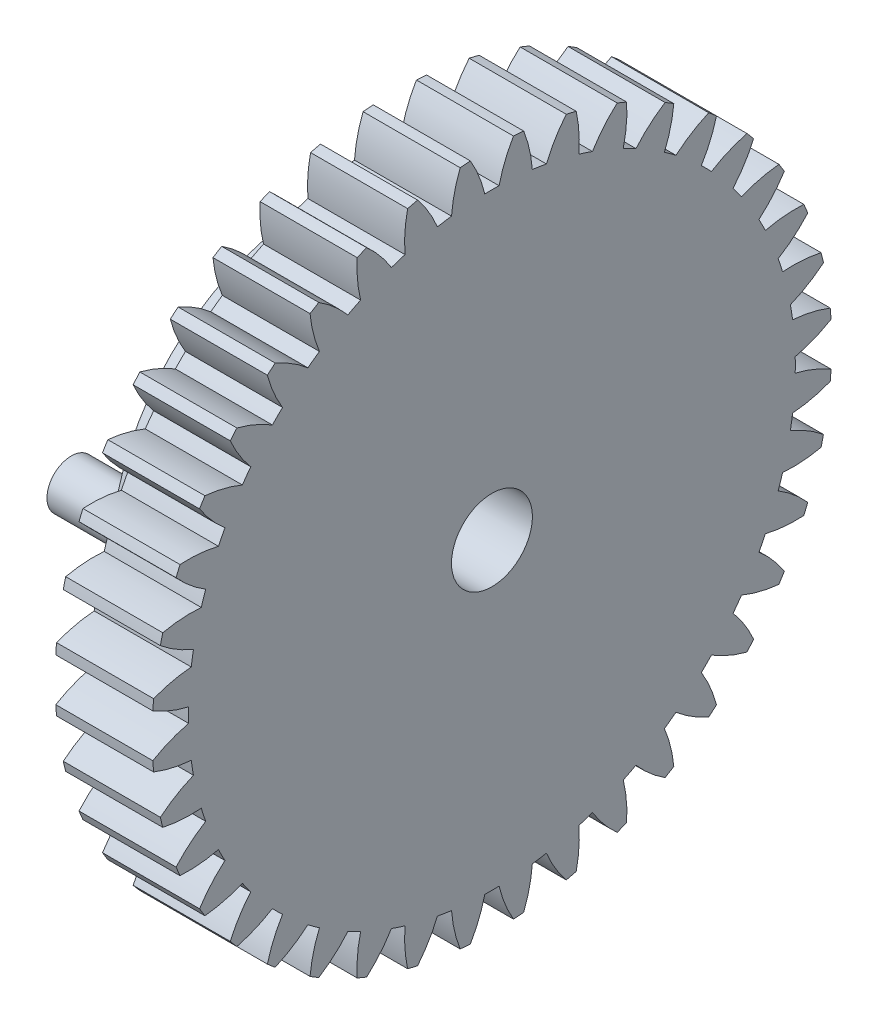
SolidWorks part; units mm, degrees
ref_plane "Plane1" through (0, 0, 0) normal (0, 0, 1) x (1, 0, 0)
ref_plane "Plane2" through (0, 0, 0) normal (0, 1, 0) x (1, 0, 0)
ref_plane "Plane3" through (0, 0, 0) normal (1, 0, 0) x (0, 0, -1)
sketch "HoldingSke" plane through (0, 0, 0) normal (0, 1, 0) x (1, 0, 0)
  line L0 (0, 0) -> (0.383, -0.3214)
  line L1 (-15, 0) -> (100, 0) construction
  line L2 (0, 0) -> (-2.1039, 2.3779)
  line L3 (0, 0) -> (-11.863, 4.5341)
  line L4 (0, 0) -> (6.6156, 5.5511)
  line L5 (0, 0) -> (-46.8476, -17.4728)
  line L6 (0, 0) -> (-9.9476, -6.7116)
  line L7 (-2.1039, 2.3779) -> (8.6586, 51.2059)
  line L8 (-76.2, 54.61) -> (-74.4, 54.61)
  line L9 (-71.009, 38.7566) -> (-53.1078, 45.2721)
  line L10 (-76.2, 71.12) -> (104.1128, 71.12)
  line L11 (0, 0) -> (-12, 0)
  line L12 (-76.2, 101.6) -> (-76.133, 101.6)
  line L13 (24.9733, 27.94) -> (52.9518, 28.4284)
  line L14 (24.9733, 27.94) -> (24.9743, 27.94)
  line L15 (24.9733, 27.94) -> (100.4006, 29.5858)
  line L16 (-63.627, -2) -> (-12.827, -2)
  circle A0 centre (0, 0) radius 5
  circle A1 centre (0, 0) radius 37.499
  circle A2 centre (0, 0) radius 37.5
  circle A3 centre (0, 0) radius 5
  dimension "Num_teeth" = 40
  dimension "Pitch_radius" = 180.3128
  dimension "Width" = 12
  dimension "Thickness" = 12
sketch "BasProSke" plane through (0, 0, 0) normal (0, 1, 0) x (1, 0, 0)
  line L0 (-10, 0) -> (60, 0) construction
  line L1 (0, 0) -> (0, 42)
  line L2 (0, 0) -> (12, 0)
  line L3 (12, 0) -> (12, 42)
  line L4 (12, 42) -> (0, 42)
  dimension "Thickness" = 12
  dimension "Diameter" = 84
revolve "Base-Revolve" add sketch "BasProSke" angle 360 about L0
sketch "TooCutSke" plane through (0, 0, 0) normal (1, 0, 0) x (0, 0, -1)
  line L1 (0, 0) -> (0, 107) construction
  line L2 (0, 0) -> (-1.6876, 39.9644) construction
  line L3 (0, 0) -> (-6.2726, 79.7007) construction
  line L4 (-1.6876, 39.9644) -> (-3.1363, 39.8504) construction
  arc A0 (0.8828, 37.4886) -> (-0.8828, 37.4886) centre (0, 0) ccw
  arc A1 (2.6784, 41.94) -> (-2.6784, 41.94) centre (0, 0) ccw
  circle A2 centre (0, 0) radius 40 construction
  circle A3 centre (0, 0) radius 37.5877 construction
  arc A4 (-0.8828, 37.4886) -> (-2.6784, 41.94) centre (-16.451, 33.7965) ccw
  arc A5 (2.6784, 41.94) -> (0.8828, 37.4886) centre (16.451, 33.7965) ccw
extrude "ToothCut" cut sketch "TooCutSke" along normal through all
fillet "Breaks" [suppressed] radius 0.04 tangent propagation no
fillet "RootFillets" [suppressed] radius 0.501
pattern_circular "TeethCuts" count 40 every 9 about axis through (-10, 0, 0) along (1, 0, 0) of "ToothCut", "RootFillets", "Breaks"
sketch "HubNeaOneSke" plane through (0, 0, 0) normal (-1, 0, 0) x (0, 0, 1)
  circle A0 centre (0, 0) radius 37.499
  dimension "Diameter" = 74.998
extrude "HubNearOne" [suppressed] add sketch "HubNeaOneSke" along normal blind 38.0001
sketch "HubNeaBotSke" plane through (0, 0, 0) normal (-1, 0, 0) x (0, 0, 1)
  circle A0 centre (0, 0) radius 37.499
  dimension "Diameter" = 74.998
extrude "HubNearBoth" [suppressed] add sketch "HubNeaBotSke" along normal blind 19
ref_plane "FarPln" through (12, 0, 0) normal (1, 0, 0) x (0, 0, -1)
sketch "HubFarSke" plane through (12, 0, 0) normal (1, 0, 0) x (0, 0, -1)
  circle A0 centre (0, 0) radius 37.499
  dimension "Diameter" = 74.998
extrude "HubFar" [suppressed] add sketch "HubFarSke" along normal blind 19
sketch "BorSke" plane through (0, 0, 0) normal (1, 0, 0) x (0, 0, -1)
  circle A0 centre (0, 0) radius 5
  dimension "Diameter" = 10
extrude "Bore" cut sketch "BorSke" along normal mid plane 100.0001
sketch "KeySke" plane through (0, 0, 0) normal (1, 0, 0) x (0, 0, -1)
  line L0 (-1.5, 0) -> (-1.5, 6.8)
  line L1 (-1.5, 6.8) -> (1.5, 6.8)
  line L2 (1.5, 6.8) -> (1.5, 0)
  line L3 (0, 0) -> (0, 34) construction
  line L4 (-1.5, 0) -> (1.5, 0)
  dimension "Width" = 3
extrude "Keyway" [suppressed] cut sketch "KeySke" along normal mid plane 100.0001
pattern_circular "Keyway2" [suppressed] count 2 every 90 about axis through (-10, 0, 0) along (1, 0, 0)
sketch "Sketch1" plane through (0, 0, 0) normal (-1, 0, 0) x (0, 0, 1)
  circle A0 centre (0, 0) radius 25
  circle A2 centre (0, 0) radius 5
  circle A3 centre (20, 0) radius 3
  circle A4 centre (-20, 0) radius 3
  point P16 (0, 0)
  dimension "D1" = 2
extrude "Boss-Extrude1" add sketch "Sketch1" along normal blind 10
extrude "Boss-Extrude2" add sketch "Sketch1<2>" along normal blind 20 separate body contours A4
sketch "Sketch1<2>" plane through (0, 0, 0) normal (-1, 0, 0) x (0, 0, 1) same geometry as "Sketch1"
extrude "Boss-Extrude3" add sketch "Sketch1<3>" along normal blind 20 separate body contours A3
sketch "Sketch1<3>" plane through (0, 0, 0) normal (-1, 0, 0) x (0, 0, 1) same geometry as "Sketch1"
equation "' \"Module@HoldingSke\" = 6.35"
equation "' \"Num_teeth@HoldingSke\" = 12"
equation "' \"Ap@HoldingSke\" =  20"
equation "' \"Ap@HoldingSke\" = 20"
equation "' \"Width@HoldingSke\" = 0.5 * 25.4"
equation "' \"Hub_dia@HoldingSke\"= 1 * 25.4"
equation "' \"Hub_dia@HoldingSke\" = 1 * 25.4"
equation "' \"Overall_len@HoldingSke\" = 1.0 * 25.4"
equation "' \"Bore@HoldingSke\" = 0.75 * 25.4"
equation "' \"T_dim@HoldingSke\" = 0.1 * 25.4"
equation "' \"Width@KeySke\" = 0.25 * 25.4"
equation "' \"Show_teeth@HoldingSke\" = 13"
equation "' \"Backlash@HoldingSke\" = 0.009 * 25.4"
equation "' \"Addendum_fac@HoldingSke\" = 1.0"
equation "' \"Dedendum_fac@HoldingSke\" = 1.25"
equation "' \"Dedendum_add@HoldingSke\" = 0.00005 * 25.4"
equation "' \"Clearance_fac@HoldingSke\" = 0.25"
equation "\"Pitch@HoldingSke\" = 1 / \"Module@HoldingSke\""
equation "\"Overcut_dia@TooCutSke\" = (\"Num_teeth@HoldingSke\" + 2 * \"Addendum_fac@HoldingSke\") / \"Pitch@HoldingSke\" + 0.002 * 25.4"
equation "\"Pitch_dia@TooCutSke\" = \"Num_teeth@HoldingSke\" / \"Pitch@HoldingSke\""
equation "\"Base_dia@TooCutSke\" = \"Num_teeth@HoldingSke\" / \"Pitch@HoldingSke\" * cos((\"Ap@HoldingSke\"  * 3.14159265 / 180))"
equation "\"Root_dia@TooCutSke\" = (\"Num_teeth@HoldingSke\" + 2) / \"Pitch@HoldingSke\" - 2 * (\"Addendum_fac@HoldingSke\" + \"Dedendum_fac@HoldingSke\") / \"Pitch@HoldingSke\" - \"Dedendum_add@HoldingSke\" * 2"
equation "\"Half_ang@TooCutSke\" = 180 / \"Num_teeth@HoldingSke\""
equation "\"Half_CT@TooCutSke\" = \"Num_teeth@HoldingSke\" / \"Pitch@HoldingSke\" * sin((3.14159265 / 2 / \"Num_teeth@HoldingSke\")) / 2 - 7 * \"Backlash@HoldingSke\" / 4"
equation "\"Flank_rad@TooCutSke\" = \"Num_teeth@HoldingSke\" / \"Pitch@HoldingSke\" / 5"
equation "\"Radius@RootFillets\" = \"Clearance_fac@HoldingSke\" / \"Pitch@HoldingSke\" + \"Dedendum_add@HoldingSke\""
equation "\"Break_rad@Breaks\" = 0.02 / \"Pitch@HoldingSke\""
equation "\"Thickness@HoldingSke\" = \"Width@HoldingSke\""
equation "\"OAL@HoldingSke\" = \"Thickness@HoldingSke\""
equation "\"MHD@HoldingSke\" = (\"Num_teeth@HoldingSke\" + 2) / \"Pitch@HoldingSke\" - 2 * (\"Addendum_fac@HoldingSke\" + \"Dedendum_fac@HoldingSke\")  / \"Pitch@HoldingSke\" - \"Dedendum_add@HoldingSke\" * 2"
equation "\"MBD@HoldingSke\" = (\"Num_teeth@HoldingSke\" + 2) / \"Pitch@HoldingSke\" - 2 * (\"Addendum_fac@HoldingSke\" + \"Dedendum_fac@HoldingSke\")  / \"Pitch@HoldingSke\" - \"Dedendum_add@HoldingSke\" * 2 - 0.002 * 25.4"
equation "\"MHD@HoldingSke\" = ((sgn( \"MHD@HoldingSke\" - \"Hub_dia@HoldingSke\" )-1)*( \"MHD@HoldingSke\" - \"Hub_dia@HoldingSke\" ))/-2+ \"Hub_dia@HoldingSke\""
equation "\"MBD@HoldingSke\" = ((sgn( \"MBD@HoldingSke\" - \"Bore@HoldingSke\" )-1)*( \"MBD@HoldingSke\" - \"Bore@HoldingSke\" ))/-2+ \"Bore@HoldingSke\""
equation "\"OAL@HoldingSke\" = ((sgn( \"OAL@HoldingSke\" - \"Overall_len@HoldingSke\" )+1)*( \"OAL@HoldingSke\" - \"Overall_len@HoldingSke\" ))/2 + \"Overall_len@HoldingSke\" + 0.000002 * 25.4"
equation "\"Num_teeth@TeethCuts\" = int( \"Show_teeth@HoldingSke\" ) + 1"
equation "\"Num_teeth@TeethCuts\" = ((sgn( \"Num_teeth@TeethCuts\" - \"Num_teeth@HoldingSke\" )-1)*( \"Num_teeth@TeethCuts\" - \"Num_teeth@HoldingSke\" ))/-2+ \"Num_teeth@HoldingSke\""
equation "\"Num_teeth@TeethCuts\" = ((sgn( \"Num_teeth@TeethCuts\" - 2.0)+1)*( \"Num_teeth@TeethCuts\" - 2.0))/2 +2.0"
equation "\"Angle@TeethCuts\" = 360.0 / \"Num_teeth@HoldingSke\""
equation "\"Diameter@BasProSke\" = (\"Num_teeth@HoldingSke\" + 2 * \"Addendum_fac@HoldingSke\") / \"Pitch@HoldingSke\""
equation "\"Thickness@BasProSke\"  = \"Thickness@HoldingSke\""
equation "' \"Fillet_rad@BasProSke\" =  \"Thickness@HoldingSke\" * 0.05"
equation "' \"Fillet_rad@BasProSke\" = \"Thickness@HoldingSke\" * 0.05"
equation "\"MHD@HoldingSke\" = ((sgn( \"MHD@HoldingSke\" - \"Root_dia@TooCutSke\" )-1)*( \"MHD@HoldingSke\" - \"Root_dia@TooCutSke\" ))/-2+ \"Root_dia@TooCutSke\""
equation "\"Diameter@HubNeaOneSke\" = \"MHD@HoldingSke\""
equation "\"Length@HubNearOne\" = \"OAL@HoldingSke\" - \"Thickness@BasProSke\""
equation "\"Diameter@HubNeaBotSke\" = \"MHD@HoldingSke\""
equation "\"Length@HubNearBoth\" = ( \"OAL@HoldingSke\" - \"Thickness@BasProSke\" ) / 2.0"
equation "\"Thickness@FarPln\" = \"Thickness@BasProSke\""
equation "\"Diameter@HubFarSke\" = \"MHD@HoldingSke\""
equation "\"Length@HubFar\" = ( \"OAL@HoldingSke\" - \"Thickness@BasProSke\" ) / 2.0"
equation "\"Diameter@BorSke\" = \"MBD@HoldingSke\""
equation "\"D1@Bore\" = \"OAL@HoldingSke\" * 2.0"
equation "\"D1@Keyway\" = \"OAL@HoldingSke\" * 2.0"
equation "\"Offset@KeySke\" = \"T_dim@HoldingSke\" + \"MBD@HoldingSke\" / 2.0"
